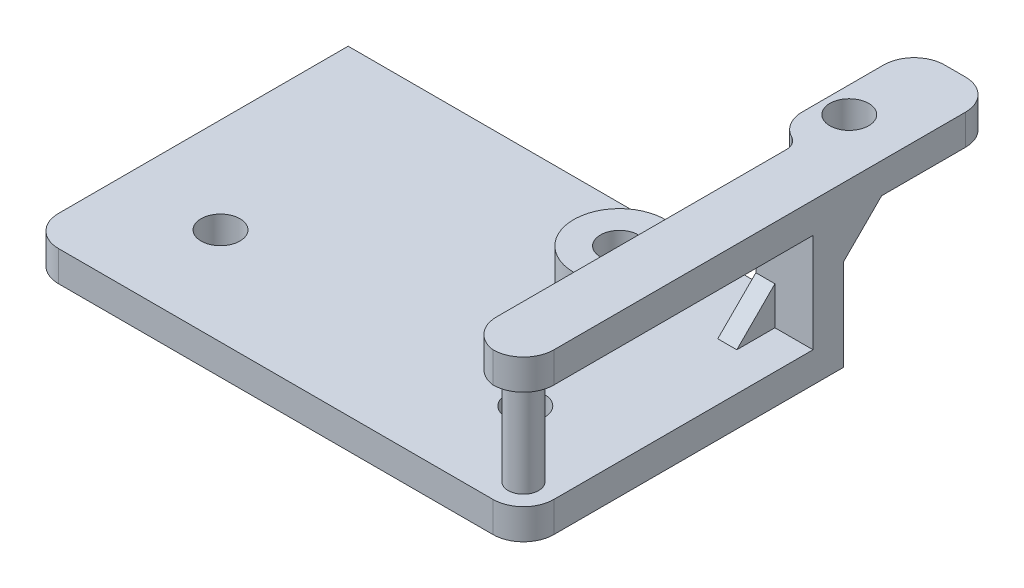
SolidWorks part; units mm, degrees
ref_plane "Front Plane" through (0, 0, 0) normal (0, 0, 1) x (1, 0, 0)
ref_plane "Top Plane" through (0, 0, 0) normal (0, 1, 0) x (1, 0, 0)
ref_plane "Right Plane" through (0, 0, 0) normal (1, 0, 0) x (0, 0, -1)
sketch "Sketch1" plane through (0, 0, 0) normal (0, 1, 0) x (1, 0, 0)
  line L1 (4, 0) -> (61, 0)
  line L2 (0, 4) -> (0, 42)
  line L3 (0, 42) -> (65, 42)
  line L4 (65, 4) -> (65, 42)
  arc A0 (65, 4) -> (61, 0) centre (61, 4) cw
  arc A1 (0, 4) -> (4, 0) centre (4, 4) ccw
  circle A2 centre (12.5, 12.75) radius 2.55
  circle A3 centre (52.5, 12.75) radius 2.55
  point P7 (65, 0)
  point P10 (0, 0)
  dimension "D3" = 4
  dimension "D8" = 5.1
  dimension "D9" = 5.1
  dimension "D1" = 42
  dimension "D2" = 65
  dimension "D4" = 12.75
  dimension "D5" = 40
  dimension "D6" = 12.75
  dimension "D7" = 12.5
extrude "Boss-Extrude1" add sketch "Sketch1" along normal blind 4
sketch "Sketch2" plane through (0, 4, 0) normal (0, 1, 0) x (1, 0, 0)
  line L0 (0, 42) -> (0, 4) construction
  line L1 (65, 42) -> (0, 42)
  line L2 (65, 42) -> (65, 38)
  line L3 (65, 38) -> (0, 38)
  line L4 (0, 42) -> (0, 38)
  circle A0 centre (61, 4) radius 2
  circle A1 centre (4, 4) radius 2
  dimension "D1" = 4
  dimension "D2" = 4
  dimension "D3" = 4
extrude "Boss-Extrude2" add sketch "Sketch2" along normal blind 13
sketch "Sketch3" plane through (0, 17, 0) normal (0, 1, 0) x (1, 0, 0)
  line L0 (4, 0) -> (61, 0) construction
  line L1 (0, 42) -> (65, 42)
  line L2 (0, 42) -> (0, 4)
  line L3 (4, 0) -> (61, 0)
  line L4 (65, 42) -> (65, 4)
  arc A0 (0, 4) -> (4, 0) centre (4, 4) ccw
  arc A1 (61, 0) -> (65, 4) centre (61, 4) ccw
  dimension "D1" = 4
  dimension "D2" = 0
  dimension "D3" = 65
extrude "Boss-Extrude3" add sketch "Sketch3" along normal blind 4
sketch "Sketch4" plane through (0, 0, -42) normal (0, 0, -1) x (-1, 0, 0)
  line L0 (-65, 21) -> (-65, 0) construction
  line L1 (-65, 17) -> (0, 17)
  line L2 (-65, 17) -> (-65, 21)
  line L3 (-65, 21) -> (0, 21)
  line L4 (0, 17) -> (0, 21)
  dimension "D1" = 4
extrude "Boss-Extrude4" add sketch "Sketch4" along normal blind 20
fillet "Fillet1" radius 4 2 edges at (65, 19, -62) (0, 19, -62)
sketch "Sketch6" plane through (0, 21, 0) normal (0, 1, 0) x (1, 0, 0)
  line L0 (65, 50.1043) -> (57.65, 50.1043)
  line L1 (4, 62) -> (61, 62) construction
  line L2 (57.65, 0) -> (57.65, 62)
  line L3 (65, 4) -> (65, 58) construction
  line L6 (45.5, 32.1043) -> (65, 32.1043)
  line L8 (45.5, 0) -> (45.5, 62)
  circle A0 centre (57.65, 50.1043) radius 2.55
  circle A1 centre (45.5, 32.1043) radius 2.55
  dimension "D2" = 5.1
  dimension "D3" = 0
  dimension "D4" = 5.1
  dimension "D1" = 62
  dimension "D5" = 62
  dimension "D6" = 29.8957
  dimension "D7" = 11.8957
  dimension "D8" = 0
  dimension "D9" = 0
  dimension "D10" = 7.35
  dimension "D11" = 12.15
  dimension "D12" = 7.35
  dimension "D13" = 11.8957
  dimension "D14" = 29.8957
extrude "Cut-Extrude1" cut sketch "Sketch6" against normal blind 20 contours L8 A1 | L8 A1 L6 | L6 A1 L8 | L2 A0 L0 | A0 region at (58.7323, 21, -49.0221) region at (46.5823, 21, -31.0221) region at (46.5823, 21, -33.1866) region at (44.4177, 21, -32.1043)
sketch "Sketch7" plane through (0, 0, 0) normal (0, 0, 1) x (1, 0, 0)
  line L0 (4, 21) -> (61, 21) construction
  line L1 (50, 21) -> (0, 21)
  line L2 (50, 21) -> (50, 0)
  line L3 (50, 0) -> (0, 0)
  line L4 (0, 21) -> (0, 0)
  line L5 (50, 4) -> (0, 4)
  line L6 (4, 4) -> (61, 4) construction
  line M5 (4, 17) -> (61, 17)
  line M7 (61, 21) -> (4, 21)
  line M8 (4, 21) -> (4, 17)
  dimension "D1" = 50
extrude "Cut-Extrude2" cut sketch "Sketch7" against normal blind 80 contours L5 L2 L1 L4 M5 M8 | L2 M7 M8 M5 region at (27, 19, 0) region at (24.4474, 10.7042, 0)
ref_plane "Plane1" through (57.5, 0, 0) normal (1, 0, 0) x (0, 0, -1)
sketch "Sketch10" plane through (57.5, 0, 0) normal (1, 0, 0) x (0, 0, -1)
  line L0 (33, 4) -> (38, 9)
  line L1 (4, 4) -> (38, 4) construction
  line L2 (38, 17) -> (38, 4) construction
  line L3 (38, 9) -> (38, 4)
  line L4 (38, 4) -> (33, 4)
  dimension "D1" = 5
  dimension "D2" = 5
extrude "Boss-Extrude6" add sketch "Sketch10" along normal blind 2.5 and the other way blind 2.5
sketch "Sketch11" plane through (0, 21, 0) normal (0, 1, 0) x (1, 0, 0)
  line L0 (57.5, 0) -> (57.5, 42)
  line L1 (50, 0) -> (61, 0) construction
  line L2 (57.5, -11.55) -> (57.5, 11.55) construction
  line L4 (50, 62) -> (50, 0) construction
  line L6 (50, 44) -> (50, 0)
  line L7 (50, 0) -> (57.5, 0)
  line L8 (55.5, 44) -> (50, 44)
  arc A2 (57.5, 42) -> (55.5, 44) centre (55.5, 42) ccw
  point P12 (57.5, 31)
  point P13 (57.5, 44)
  point P15 (50, 31)
  line M10 (50, 62) -> (50, 0)
  line M11 (50, 0) -> (61, 0)
  dimension "D1" = 44
  dimension "D3" = 2
  dimension "D2" = 7.5
extrude "Cut-Extrude3" cut sketch "Sketch11" against normal up to surface (17 mm away) contours L0 M10 M11 region at (53.7414, 21, -21.9438) up to face at (52.5, 4, -10.2)
fillet "Fillet2" radius 4 1 edges at (57.5, 19, 0)
sketch "Sketch8" plane through (0, 4, 0) normal (0, 1, 0) x (1, 0, 0)
  circle A0 centre (45.5, 32.1043) radius 6
  circle A1 centre (45.5, 32.1043) radius 2.5
  dimension "D1" = 5
  dimension "D2" = 12
extrude "Boss-Extrude5" add sketch "Sketch8" along normal blind 5
fillet "Fillet3" radius 4 1 edges at (50, 19, -62)
sketch "Sketch12" plane through (57.5, 0, 0) normal (1, 0, 0) x (0, 0, -1)
  line L0 (42, 12) -> (47, 17)
  line L1 (42, 17) -> (42, 0) construction
  line L2 (58, 17) -> (42, 17) construction
  line L3 (47, 17) -> (42, 17)
  line L4 (42, 17) -> (42, 12)
  dimension "D1" = 5
  dimension "D2" = 5
extrude "Boss-Extrude7" add sketch "Sketch12" along normal up to surface (7.5 mm away) from offset 4 up to face at (65, 11.8, -29.2)
sketch "Sketch13" plane through (0, 0, 0) normal (0, -1, 0) x (1, 0, 0)
  circle A0 centre (45.5, -32.1043) radius 4.5
  dimension "D1" = 9
extrude "Cut-Extrude4" cut sketch "Sketch13" against normal blind 6
sketch "Sketch14" plane through (0, 21, 0) normal (0, 1, 0) x (1, 0, 0)
  line L0 (54.2644, 44) -> (54.2644, 62)
  line L1 (55.5, 44) -> (50, 44) construction
  line L2 (54, 62) -> (61, 62) construction
  line L3 (54.2644, 62) -> (40.9821, 62)
  line L4 (40.9821, 62) -> (40.9821, 44)
  line L5 (40.9821, 44) -> (54.2644, 44)
  line L6 (50, 58) -> (50, 44) construction
  dimension "D1" = 13.2823
  dimension "D2" = 4.2644
extrude "Cut-Extrude5" cut sketch "Sketch14" against normal blind 6 contours L5 L0 L3 L4
fillet "Fillet5" radius 4 2 edges at (54.2644, 19, -62) (54.2644, 19, -44)
